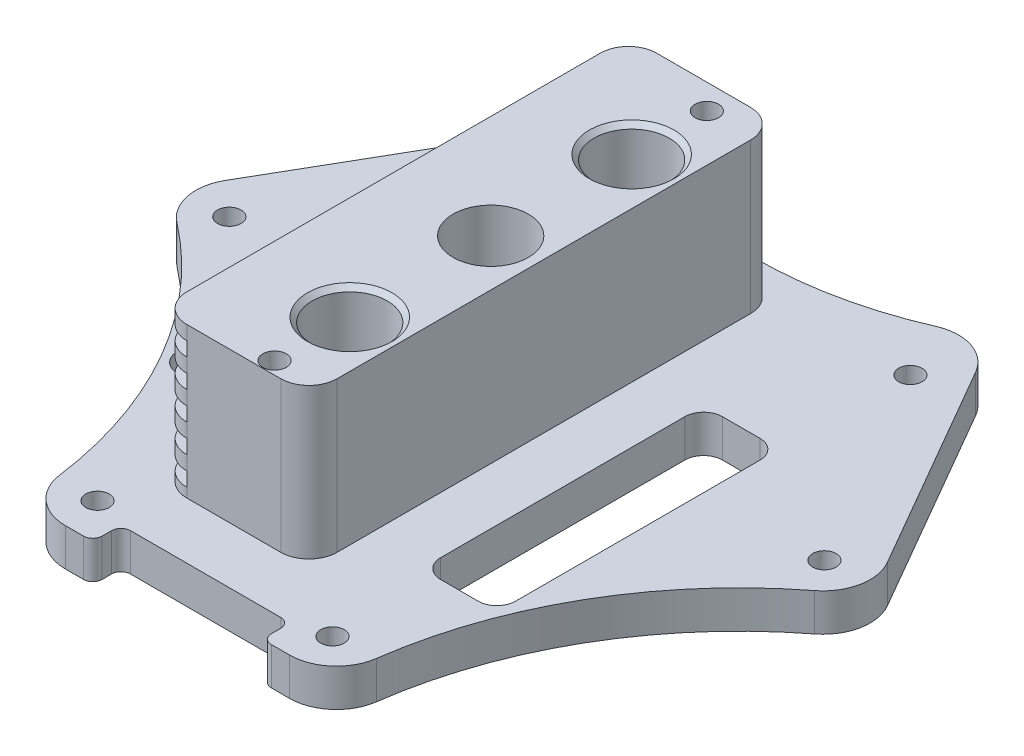
SolidWorks part; units mm, degrees
ref_plane "前基準面" through (0, 0, 0) normal (0, 0, 1) x (1, 0, 0)
ref_plane "上基準面" through (0, 0, 0) normal (0, 1, 0) x (1, 0, 0)
ref_plane "右基準面" through (0, 0, 0) normal (1, 0, 0) x (0, 0, -1)
sketch "草圖1" plane through (0, 0, 0) normal (0, 1, 0) x (1, 0, 0)
  line L0 (-20, 33.342) -> (20, 33.342) construction
  line L1 (20, 33.342) -> (37.5, 3.0311)
  line L2 (37.5, 3.0311) -> (16.5, -33.342) construction
  line L3 (16.5, -33.342) -> (-16.5, -33.342)
  line L4 (-16.5, -33.342) -> (-37.5, 3.0311) construction
  line L5 (-37.5, 3.0311) -> (-20, 33.342)
  line L6 (0, 33.342) -> (0, -33.342) construction
  arc A0 (-20, 33.342) -> (20, 33.342) centre (0, 67.983) ccw
  arc A1 (16.5, -33.342) -> (37.5, 3.0311) centre (61.4674, -35.0552) cw
  arc A2 (-37.5, 3.0311) -> (-16.5, -33.342) centre (-61.4674, -35.0552) cw
  dimension "D6" = 40
  dimension "D7" = 45
  dimension "D8" = 45
  dimension "D1" = 40
  dimension "D2" = 33
  dimension "D3" = 35
  dimension "D4" = 42
  dimension "D5" = 120
extrude "填料-伸長1" add sketch "草圖1" along normal blind 4
fillet "圓角1" radius 5 6 edges at (20, 2, -33.342) (-20, 2, -33.342) (-37.5, 2, -3.0311) (-16.5, 2, 33.342) (16.5, 2, 33.342) (37.5, 2, -3.0311)
sketch "草圖2" plane through (0, 4, 0) normal (0, 1, 0) x (1, 0, 0)
  line L0 (0, -17.0796) -> (0, 0) construction
  line L1 (-11, 25.658) -> (5, 25.658)
  line L2 (-11, 25.658) -> (-11, -24.342)
  line L3 (-11, -24.342) -> (5, -24.342)
  line L4 (5, 25.658) -> (5, -24.342)
  line L5 (-11.9201, -33.342) -> (11.9201, -33.342) construction
  dimension "D1" = 16
  dimension "D2" = 50
  dimension "D3" = 5
  dimension "D4" = 9
extrude "填料-伸長2" add sketch "草圖2" along normal blind 16
fillet "圓角2" radius 3 4 edges at (-11, 12, -25.658) (5, 12, -25.658) (5, 12, 24.342) (-11, 12, 24.342)
sketch "草圖3" plane through (0, 0, 24.342) normal (0, 0, 1) x (1, 0, 0)
  line L0 (-8, 20) -> (-8, 4) construction
  line L1 (-14.9251, 18.5) -> (-8, 18.5)
  line L2 (-14.9251, 18.5) -> (-14.9251, 17)
  line L3 (-14.9251, 17) -> (-8, 17)
  line L4 (-8, 18.5) -> (-8, 17)
  line L5 (-14.9251, 15.5) -> (-8, 15.5)
  line L6 (-14.9251, 15.5) -> (-14.9251, 14)
  line L7 (-14.9251, 14) -> (-8, 14)
  line L8 (-8, 15.5) -> (-8, 14)
  line L9 (-14.9251, 12.5) -> (-8, 12.5)
  line L10 (-14.9251, 12.5) -> (-14.9251, 11)
  line L11 (-14.9251, 11) -> (-8, 11)
  line L12 (-8, 12.5) -> (-8, 11)
  line L13 (-14.9251, 9.5) -> (-8, 9.5)
  line L14 (-14.9251, 9.5) -> (-14.9251, 8)
  line L15 (-14.9251, 8) -> (-8, 8)
  line L16 (-8, 9.5) -> (-8, 8)
  line L17 (-14.9251, 6.5) -> (-8, 6.5)
  line L18 (-14.9251, 6.5) -> (-14.9251, 5)
  line L19 (-14.9251, 5) -> (-8, 5)
  line L20 (-8, 6.5) -> (-8, 5)
  line L21 (-8, 20) -> (2, 20) construction
  dimension "D2" = 1.5
  dimension "D3" = 1.5
  dimension "D4" = 1.5
  dimension "D1" = 5
extrude "除料-伸長1" cut sketch "草圖3" against normal through all
sketch "草圖4" plane through (0, 4, 0) normal (0, 1, 0) x (1, 0, 0)
  line L0 (-11.9201, -33.342) -> (11.9201, -33.342) construction
  line L1 (11, 11.658) -> (19, 11.658)
  line L2 (11, 11.658) -> (11, -18.342)
  line L3 (11, -18.342) -> (19, -18.342)
  line L4 (19, 11.658) -> (19, -18.342)
  line L5 (5, -21.342) -> (5, 22.658) construction
  dimension "D1" = 30
  dimension "D2" = 15
  dimension "D3" = 6
  dimension "D4" = 8
extrude "除料-伸長2" cut sketch "草圖4" against normal through all
fillet "圓角3" radius 2 4 edges at (11, 2, 18.342) (11, 2, -11.658) (19, 2, -11.658) (19, 2, 18.342)
sketch "草圖5" plane through (0, 20, 0) normal (0, 1, 0) x (1, 0, 0)
  circle A0 centre (0, 0) radius 4
  dimension "D1" = 8
extrude "除料-伸長3" cut sketch "草圖5" against normal through all
sketch "草圖6" plane through (0, 4, 0) normal (0, 1, 0) x (1, 0, 0)
  line L0 (-11, -21.342) -> (-11, 22.658) construction
  line L1 (-22, 7.658) -> (-16, 7.658)
  line L2 (-22, 7.658) -> (-22, -13.342)
  line L3 (-22, -13.342) -> (-16, -13.342)
  line L4 (-16, 7.658) -> (-16, -13.342)
  line L5 (13, -18.342) -> (17, -18.342) construction
  point P4 (-11, 0.658)
  point P7 (15, -18.342)
  dimension "D1" = 6
  dimension "D2" = 5
  dimension "D3" = 5
  dimension "D4" = 21
extrude "除料-伸長4" cut sketch "草圖6" against normal through all
fillet "圓角4" radius 2 4 edges at (-22, 2, -7.658) (-16, 2, 13.342) (-16, 2, -7.658) (-22, 2, 13.342)
sketch "草圖7" plane through (0, 0, 0) normal (0, -1, 0) x (1, 0, 0)
  line L0 (0, 15) -> (0, -15) construction
  circle A0 centre (0, 15) radius 4
  circle A1 centre (0, -15) radius 4
  dimension "D1" = 8
  dimension "D2" = 8
  dimension "D3" = 15
extrude "除料-伸長5" cut sketch "草圖7" against normal through all
chamfer "導角1" distance 0.5 angle 45 2 edges at (0, 20, -19) (0, 20, 11)
hole_wizard "M10x1.0 螺紋孔1" positions "草圖9" profile "草圖8" tap size "M10x1.0" standard "Iso"
sketch "草圖9" plane through (0, 0, 0) normal (0, -1, 0) x (-1, 0, 0)
  point P0 (0, 15)
  point P3 (0, -15)
sketch "草圖8" plane through (0, 0, -15) normal (1, 0, 0) x (0, 0, -1)
  line L0 (0, 0) -> (0, 6.7039)
  line L1 (0, 6.7039) -> (4.5, 4)
  line L2 (4.5, 4) -> (4.5, 0)
  line L5 (4.5, 0) -> (0, 0)
  line L10 (0, 6.7039) -> (-4.5, 4) construction
  line L11 (0, -6.35) -> (0, 107.95) construction
  dimension "螺孔鑽直徑" = 9
  dimension "螺孔鑽深度" = 4
  dimension "導頭角度" = 118
cosmetic thread "鑽孔螺紋1" parameters "D1"=4, "D2"=10
cosmetic thread "鑽孔螺紋2" parameters "D1"=4, "D2"=10
sketch "草圖10" plane through (0, 0, 0) normal (0, -1, 0) x (1, 0, 0)
  line L0 (0, 23) -> (0, -23) construction
  circle A0 centre (0, 23) radius 1
  circle A1 centre (0, -23) radius 1
  point P5 (0, 0)
  dimension "D1" = 23
  dimension "D2" = 2
  dimension "D3" = 2
extrude "除料-伸長6" cut sketch "草圖10" against normal through all
hole_wizard "M3 螺紋孔1" positions "3D草圖1" profile "草圖11" tap size "M3" standard "Iso" end condition through all
sketch3d "3D草圖1"
  line L0 (0, 20, 23) -> (0, 0, 23) construction
  line L1 (0, 20, -23) -> (0, 0, -23) construction
  point P0 (0, 20, 23)
  point P4 (0, 20, -23)
sketch "草圖11" plane through (0, 20, 23) normal (1, 0, 0) x (0, 0, 1)
  line L0 (0, 0) -> (0, 20)
  line L1 (0, 20) -> (1.25, 20)
  line L2 (1.25, 20) -> (1.25, 0)
  line L5 (1.25, 0) -> (0, 0)
  line L11 (0, -6.35) -> (0, 107.95) construction
  dimension "貫穿螺孔鑽直徑" = 2.5
  dimension "貫穿螺孔鑽深度" = 20
cosmetic thread "鑽孔螺紋3" parameters "D2"=3
cosmetic thread "鑽孔螺紋4" parameters "D2"=3
sketch "草圖12" plane through (0, 4, 0) normal (0, 1, 0) x (1, 0, 0)
  line L0 (-16.9325, 22.6551) -> (-22.9325, 12.2628)
  line L1 (-22.9325, 12.2628) -> (-17.7363, 9.2628)
  line L2 (-17.7363, 9.2628) -> (-11.7363, 19.6551)
  line L3 (-11.7363, 19.6551) -> (-16.9325, 22.6551)
  line L4 (-22.3607, 29.2532) -> (-35.21, 6.9974) construction
  dimension "D1" = 8
  dimension "D2" = 6
  dimension "D3" = 12
  dimension "D4" = 3
extrude "除料-伸長7" cut sketch "草圖12" against normal through all
fillet "圓角5" radius 3 4 edges at (-11.7363, 2, -19.6551) (-17.7363, 2, -9.2628) (-22.9325, 2, -12.2628) (-16.9325, 2, -22.6551)
sketch "草圖17" plane through (0, 0, 0) normal (0, -1, 0) x (1, 0, 0)
  line L0 (-11.9201, 33.342) -> (11.9201, 33.342) construction
  line L1 (-9, 33.342) -> (9, 33.342)
  line L2 (-9, 33.342) -> (-9, 30.342)
  line L3 (-9, 30.342) -> (9, 30.342)
  line L4 (9, 33.342) -> (9, 30.342)
  line L5 (0, 0) -> (0, 30.342) construction
  dimension "D1" = 18
  dimension "D2" = 3
extrude "除料-伸長10" cut sketch "草圖17" against normal blind 4
sketch "草圖18" plane through (0, 4, 0) normal (0, 1, 0) x (1, 0, 0)
  line L0 (-12.5, -29.342) -> (12.5, -29.342) construction
  line L1 (0, 0) -> (0, -29.342) construction
  line L2 (9, -33.342) -> (11.9201, -33.342) construction
  circle A0 centre (-12.5, -29.342) radius 1
  circle A1 centre (12.5, -29.342) radius 1
  dimension "D3" = 2
  dimension "D4" = 2
  dimension "D1" = 25
  dimension "D2" = 4
extrude "除料-伸長11" cut sketch "草圖18" against normal through all
hole_wizard "M3 螺紋孔3" positions "3D草圖2" profile "草圖19" tap size "M3" standard "Iso" end condition through all
sketch3d "3D草圖2"
  line L0 (-12.5, 0, 29.342) -> (-12.5, 4, 29.342) construction
  line L1 (12.5, 0, 29.342) -> (12.5, 4, 29.342) construction
  point P0 (-12.5, 4, 29.342)
  point P4 (12.5, 4, 29.342)
sketch "草圖19" plane through (-12.5, 4, 29.342) normal (1, 0, 0) x (0, 0, 1)
  line L0 (0, 0) -> (0, 4)
  line L1 (0, 4) -> (1.25, 4)
  line L2 (1.25, 4) -> (1.25, 0)
  line L5 (1.25, 0) -> (0, 0)
  line L11 (0, -6.35) -> (0, 107.95) construction
  dimension "貫穿螺孔鑽直徑" = 2.5
  dimension "貫穿螺孔鑽深度" = 4
cosmetic thread "鑽孔螺紋7" parameters "D2"=3
cosmetic thread "鑽孔螺紋8" parameters "D2"=3
pattern_circular "環狀複製排列14" count 3 over 360 about axis through (0, 0, 0) along (0, 1, 0) of "除料-伸長11", "M3 螺紋孔3"
fillet "圓角8" radius 1 4 edges at (9, 2, 33.342) (9, 2, 30.342) (-9, 2, 33.342) (-9, 2, 30.342)
